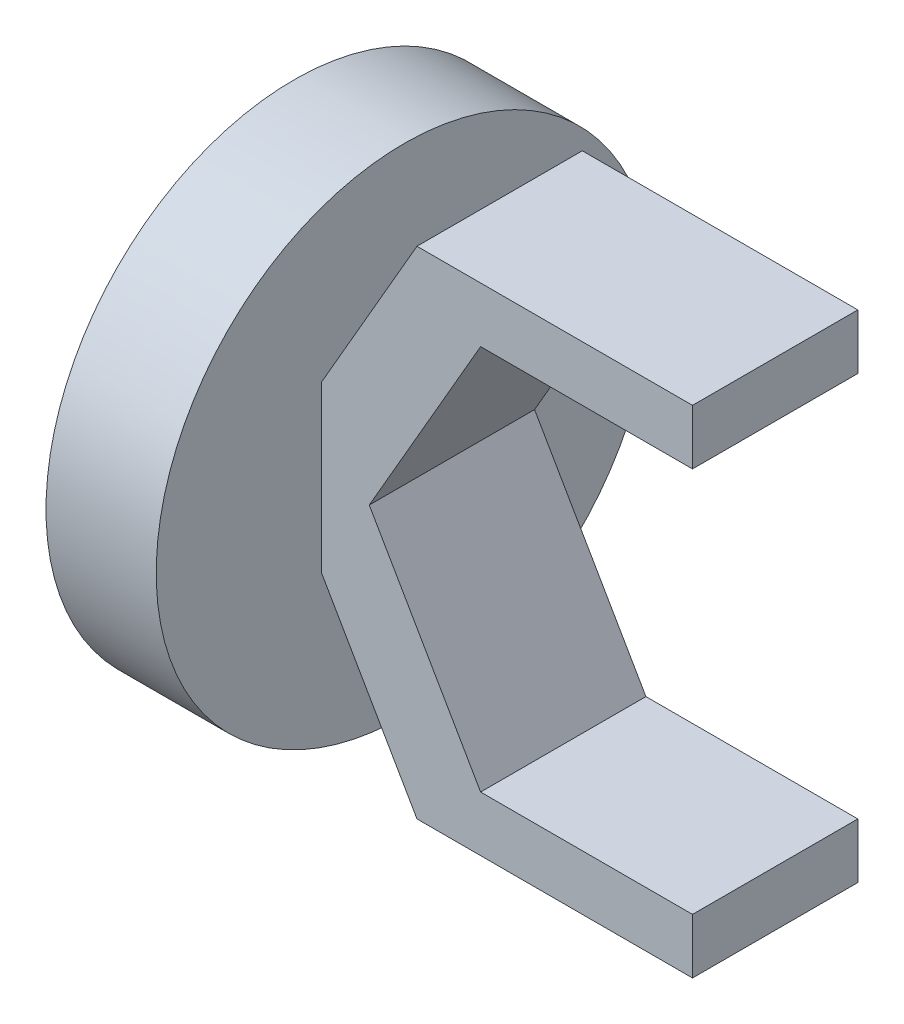
SolidWorks part; units mm, degrees
ref_plane "Front Plane" through (0, 0, 0) normal (0, 0, 1) x (1, 0, 0)
ref_plane "Top Plane" through (0, 0, 0) normal (0, 1, 0) x (1, 0, 0)
ref_plane "Right Plane" through (0, 0, 0) normal (1, 0, 0) x (0, 0, -1)
sketch "Sketch1" plane through (0, 0, 0) normal (1, 0, 0) x (0, 0, -1)
  circle A0 centre (0, 0) radius 45
  circle A1 centre (0, 0) radius 10
  dimension "D1" = 90
  dimension "D2" = 20
extrude "Boss-Extrude1" add sketch "Sketch1" along normal blind 20
sketch "Sketch2" plane through (20, 0, 0) normal (1, 0, 0) x (0, 0, -1)
  line L0 (0, -15) -> (0, 15) construction
  line L2 (12.5, -15) -> (-12.5, -15)
  line L3 (12.5, -15) -> (12.5, 15)
  line L4 (12.5, 15) -> (-12.5, 15)
  line L5 (-12.5, -15) -> (-12.5, 15)
  line L6 (12.5, -15) -> (-12.5, 15) construction
  line L7 (12.5, 15) -> (-12.5, -15) construction
  point P0 (0, 0)
  point P5 (0, 0)
  dimension "D1" = 30
  dimension "D2" = 25
  dimension "D3" = 30
sketch "Sketch3" plane through (0, 0, 0) normal (0, 0, 1) x (1, 0, 0)
  line L0 (20, 0) -> (46.0231, -45.0733) construction
  line L1 (20, -15) -> (20, 15) construction
  line L2 (20, -45) -> (70.3127, -45) construction
  line L3 (20, -15) -> (20, 15) construction
  line L4 (20, 0) -> (50020, 0) construction
  dimension "D1" = 30
sketch "Sketch4" plane through (0, 0, 0) normal (0, 0, 1) x (1, 0, 0)
  line L0 (0, 0) -> (50000, 0) construction
  line L1 (20, -15) -> (20, 15) construction
  line L2 (20, -45) -> (20, 45) construction
  line L3 (20, -15) -> (37.3205, -45)
  line L6 (20, 0) -> (46.0231, -45.0733) construction
  line L7 (20, -45) -> (70.3127, -45) construction
  line L8 (37.3205, -45) -> (87.3205, -45)
  line L9 (87.3205, -45) -> (87.3205, -35)
  line L10 (48.8675, -35) -> (28.6603, 0)
  line L11 (48.8675, -35) -> (87.3205, -35)
  line L12 (-199980, 0) -> (250020, 0) construction
  line L13 (0, 45) -> (0, -45) construction
  line L14 (48.8675, 35) -> (87.3205, 35)
  line L15 (48.8675, 35) -> (28.6603, 0)
  line L16 (87.3205, 45) -> (87.3205, 35)
  line L17 (37.3205, 45) -> (87.3205, 45)
  line L18 (20, 15) -> (37.3205, 45)
  line L19 (20, 15) -> (20, -15)
  point P23 (0, 0)
  dimension "D1" = 7.5
  dimension "D2" = 50
  dimension "D3" = 10
  dimension "D4" = 7.5
  dimension "D5" = 10
extrude "Boss-Extrude2" add sketch "Sketch4" along normal blind 15 and the other way blind 15
ref_point "Point1"
sketch "Sketch5" plane through (0, 0, 0) normal (-1, 0, 0) x (0, 0, 1)
  line L0 (0, 0) -> (66.5611, 0) construction
  line L1 (66.5611, 0) -> (66.5611, -16.7319) construction
